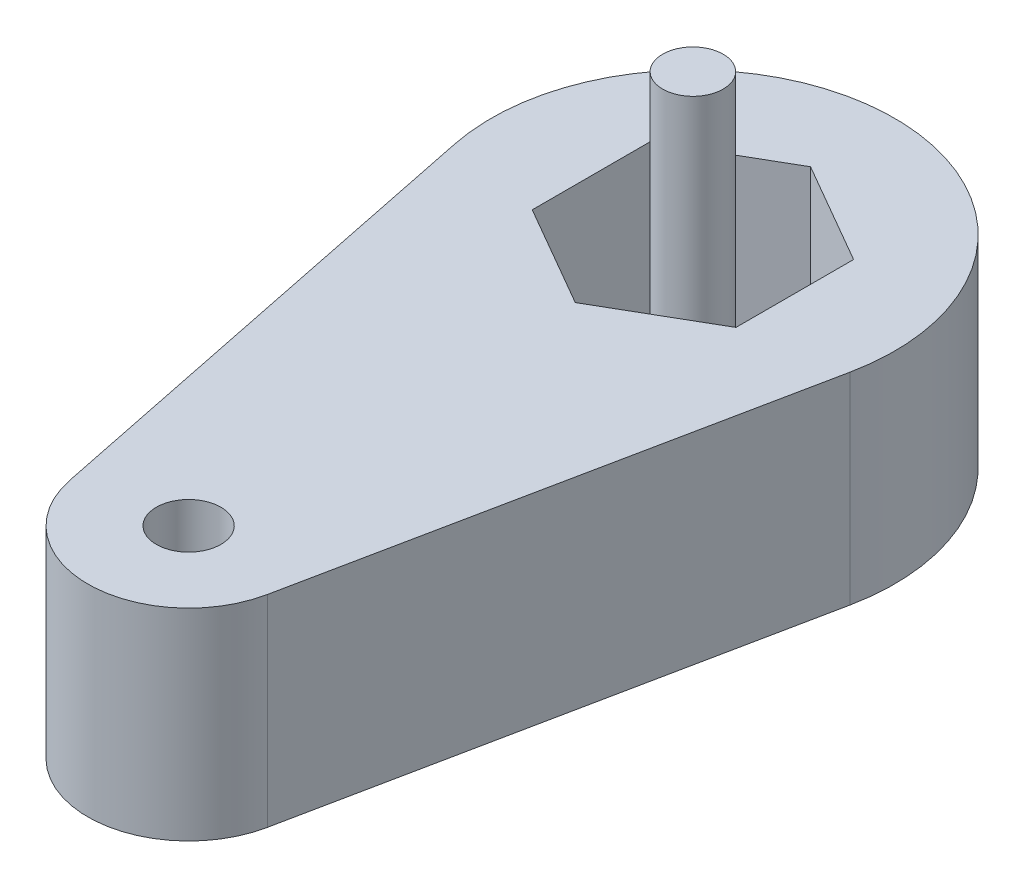
SolidWorks part; units mm, degrees
ref_plane "正面" through (0, 0, 0) normal (0, 0, 1) x (1, 0, 0)
ref_plane "平面" through (0, 0, 0) normal (0, 1, 0) x (1, 0, 0)
ref_plane "右側面" through (0, 0, 0) normal (1, 0, 0) x (0, 0, -1)
sketch "ｽｹｯﾁ1" plane through (0, 0, 0) normal (0, 1, 0) x (1, 0, 0)
  line L0 (-9.798, -2) -> (-4.899, -26)
  line L1 (4.899, -26) -> (9.798, -2)
  arc A0 (9.798, -2) -> (-9.798, -2) centre (0, 0) ccw
  arc A1 (-4.899, -26) -> (4.899, -26) centre (0, -25) ccw
  circle A2 centre (0, -25) radius 1.6
  dimension "D1" = 20
  dimension "D2" = 10
  dimension "D4" = 3.2
  dimension "D3" = 25
extrude "ﾎﾞｽ - 押し出し1" add sketch "ｽｹｯﾁ1" along normal blind 10
sketch "ｽｹｯﾁ2" plane through (0, 10, 0) normal (0, 1, 0) x (1, 0, 0)
  line L1 (0, 5.8312) -> (-5.05, 2.9156)
  line L2 (-5.05, 2.9156) -> (-5.05, -2.9156)
  line L3 (-5.05, -2.9156) -> (0, -5.8312)
  line L4 (0, -5.8312) -> (5.05, -2.9156)
  line L5 (5.05, -2.9156) -> (5.05, 2.9156)
  line L6 (5.05, 2.9156) -> (0, 5.8312)
  circle A0 centre (0, 0) radius 5.05 construction
  point P1 (0, 0)
  dimension "D1" = 10.1
extrude "ｶｯﾄ - 押し出し1" cut sketch "ｽｹｯﾁ2" against normal offset from surface (8 mm away) 2 up to face at (0, 0, 12)
sketch "ｽｹｯﾁ3" plane through (0, 2, 0) normal (0, 1, 0) x (1, 0, 0)
  circle A0 centre (0, 0) radius 1.5
  dimension "D1" = 3
extrude "ﾎﾞｽ - 押し出し2" add sketch "ｽｹｯﾁ3" along normal blind 15
